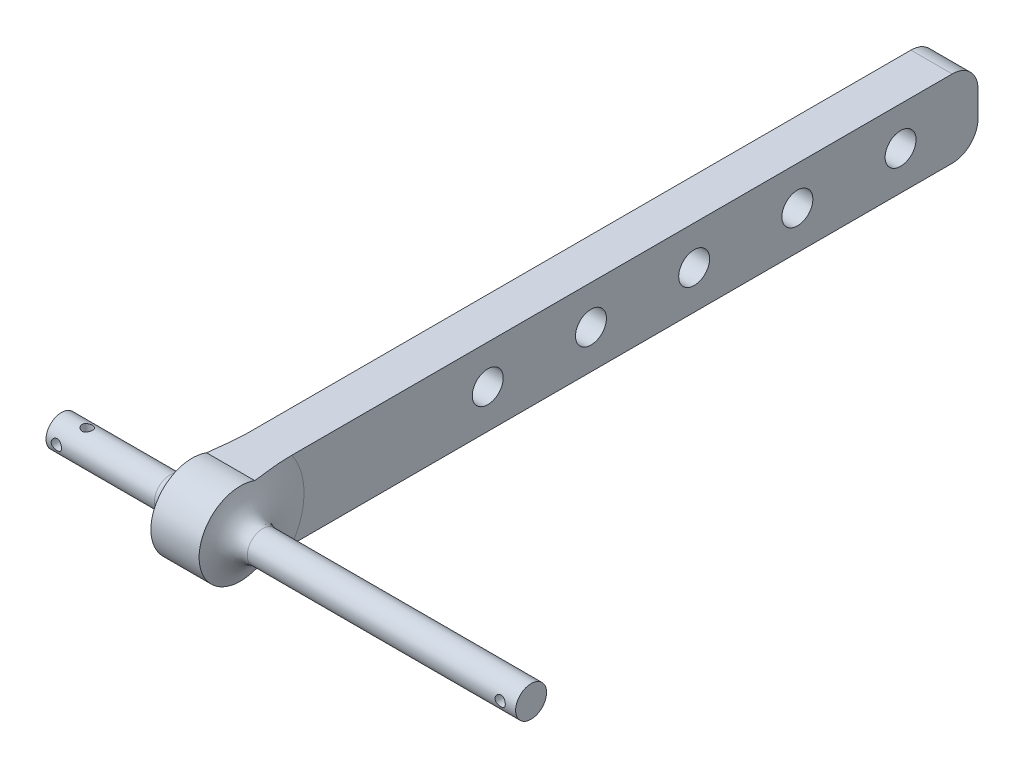
SolidWorks part; units mm, degrees
ref_plane "前视基准面" through (0, 0, 0) normal (0, 0, 1) x (1, 0, 0)
ref_plane "上视基准面" through (0, 0, 0) normal (0, 1, 0) x (1, 0, 0)
ref_plane "右视基准面" through (0, 0, 0) normal (1, 0, 0) x (0, 0, -1)
other "Configuration Table"
sketch "草图1" plane through (0, 0, 0) normal (1, 0, 0) x (0, 0, -1)
  line L1 (0, 0) -> (150, 0)
  line L2 (0, 0) -> (0, 15)
  line L3 (0, 15) -> (150, 15)
  line L4 (150, 0) -> (150, 15)
  dimension "D1" = 15
  dimension "D2" = 150
extrude "凸台-拉伸1" add sketch "草图1" along normal blind 8
fillet "圆角1" radius 5 4 edges at (4, 0, -150) (4, 15, -150) (4, 0, 0) (4, 15, 0)
sketch "草图6" plane through (8, 0, 0) normal (1, 0, 0) x (0, 0, -1)
  circle A0 centre (6.4, 7.5) radius 8
  dimension "D1" = 16
extrude "凸台-拉伸2" add sketch "草图6" against normal up to surface (8 mm away) up to face at (0, 7.5, -75)
sketch "草图15" plane through (0, 0, 0) normal (-1, 0, 0) x (0, 0, 1)
  circle A2 centre (-6.4, 7.5) radius 3
  dimension "D1" = 6
extrude "凸台-拉伸5" add sketch "草图15" along normal blind 26 and the other way blind 65
sketch "草图16" plane through (0, 0, 0) normal (0, 0, 1) x (1, 0, 0)
  line L0 (-26, 7.5) -> (-24.7951, 7.5) construction
  line L1 (-26, 10.5) -> (-26, 4.5) construction
  line L2 (65, 7.5) -> (28.4852, 7.5) construction
  line L3 (65, 4.5) -> (65, 10.5) construction
  circle A0 centre (-24, 7.5) radius 1
  circle A1 centre (62, 7.5) radius 1
  dimension "D2" = 2
  dimension "D3" = 2
  dimension "D1" = 2
  dimension "D4" = 3
extrude "切除-拉伸9" cut sketch "草图16" against normal up to next
sketch "草图17" plane through (0, 0, 0) normal (-1, 0, 0) x (0, 0, 1)
  line L0 (-150, 7.5) -> (-31.7081, 7.5) construction
  line L1 (-150, 5) -> (-150, 10) construction
  circle A0 centre (-135, 7.5) radius 3
  circle A1 centre (-115, 7.5) radius 3
  circle A2 centre (-95, 7.5) radius 3
  circle A3 centre (-75, 7.5) radius 3
  circle A4 centre (-55, 7.5) radius 3
  dimension "D6" = 6
  dimension "D7" = 6
  dimension "D8" = 6
  dimension "D9" = 6
  dimension "D10" = 6
  dimension "D1" = 15
  dimension "D2" = 20
  dimension "D3" = 20
  dimension "D4" = 20
  dimension "D5" = 20
extrude "切除-拉伸10" cut sketch "草图17" against normal up to next
sketch "草图18" plane through (0, 0, 0) normal (0, 1, 0) x (1, 0, 0)
  line L0 (-26, 6.4) -> (-12.4483, 6.4) construction
  line L1 (-26, 9.4) -> (-26, 3.4) construction
  circle A0 centre (-21, 6.4) radius 1
  dimension "D2" = 2
  dimension "D1" = 5
extrude "切除-拉伸11" cut sketch "草图18" along normal blind 15
fillet "圆角2" radius 10 1 edges at (0, 7.5, -3.4) second distance 5 first distance on face at (0, 7.5, -132)
fillet "圆角3" radius 5 1 edges at (8, 7.5, -3.4) second distance 10 first distance on face at (61.0145, 7.6699, -3.4048)
